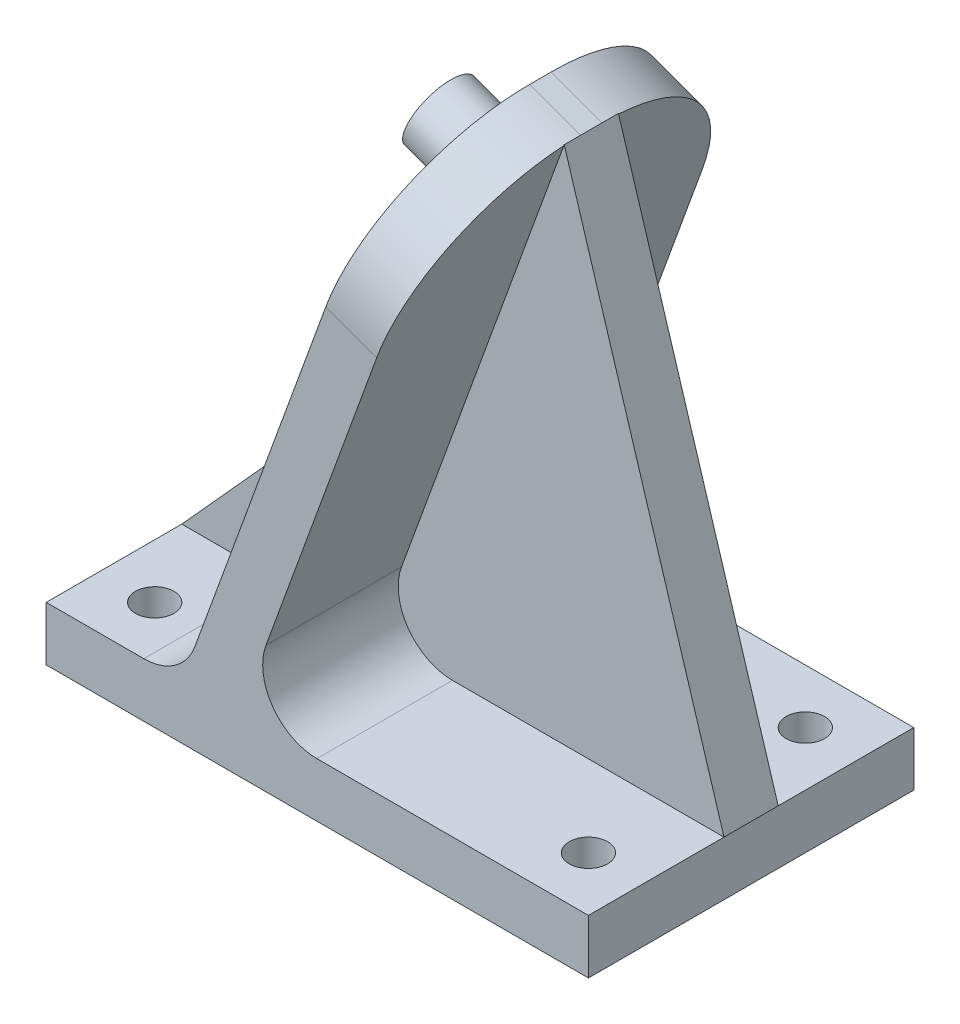
SolidWorks part; units mm, degrees
ref_plane "Front Plane" through (0, 0, 0) normal (0, 0, 1) x (1, 0, 0)
ref_plane "Top Plane" through (0, 0, 0) normal (0, 1, 0) x (1, 0, 0)
ref_plane "Right Plane" through (0, 0, 0) normal (1, 0, 0) x (0, 0, -1)
sketch "Sketch1" plane through (0, 0, 0) normal (0, 1, 0) x (1, 0, 0)
  line L1 (-31.75, -19.05) -> (31.75, -19.05)
  line L2 (-31.75, -19.05) -> (-31.75, 19.05)
  line L3 (-31.75, 19.05) -> (31.75, 19.05)
  line L4 (31.75, -19.05) -> (31.75, 19.05)
  line L5 (-31.75, -19.05) -> (31.75, 19.05) construction
  line L6 (-31.75, 19.05) -> (31.75, -19.05) construction
  point P0 (0, 0)
  dimension "D1" = 63.5
  dimension "D2" = 38.1
extrude "Boss-Extrude1" add sketch "Sketch1" along normal blind 6.35
sketch "Sketch2" plane through (0, 0, 19.05) normal (0, 0, 1) x (1, 0, 0)
  line L0 (-11.43, 0) -> (13.0366, 67.2214)
  line L1 (-11.43, 0) -> (-17.397, 2.1718)
  line L2 (13.0366, 67.2214) -> (7.0695, 69.3932)
  line L3 (-17.397, 2.1718) -> (7.0695, 69.3932)
  line L4 (-11.43, 0) -> (7.0695, 69.3932) construction
  line L5 (13.0366, 67.2214) -> (-17.397, 2.1718) construction
  line L6 (31.75, 6.35) -> (31.75, 0) construction
  line L7 (-31.75, 0) -> (31.75, 0) construction
  point P1 (-2.1802, 34.6966)
  dimension "D1" = 20
  dimension "D2" = 50.8
  dimension "D3" = 11.43
extrude "Boss-Extrude2" add sketch "Sketch2" against normal up to surface (38.1 mm away) up to face at (0, 3.175, -19.05)
fillet "Fillet1" radius 17.78 2 edges at (10.0531, 68.3073, 19.05) (10.0531, 68.3073, -19.05)
sketch "Sketch4" plane through (0, 6.35, 0) normal (0, 1, 0) x (1, 0, 0)
  circle A0 centre (25.4, -12.7) radius 2.25 construction
  circle A1 centre (-25.4, -12.7) radius 2.25 construction
  circle A2 centre (25.4, 12.7) radius 2.25 construction
  circle A3 centre (-25.4, 12.7) radius 2.25 construction
  circle A4 centre (25.4, -12.7) radius 2.25
  circle A5 centre (-25.4, -12.7) radius 2.25
  circle A6 centre (25.4, 12.7) radius 2.25
  circle A7 centre (-25.4, 12.7) radius 2.25
extrude "Cut-Extrude2" cut sketch "Sketch4" against normal through all
sketch "Sketch5" plane through (-16.06, 5.8454, 0) normal (-0.9397, 0.342, 0) x (0, 0, 1)
  line L0 (-1.27, 67.6262) -> (1.27, 67.6262) construction
  circle A0 centre (0, 54.9262) radius 5
  point P6 (0, 67.6262)
  dimension "D1" = 10
  dimension "D2" = 12.7
extrude "Boss-Extrude3" add sketch "Sketch5" along normal blind 1 contours A0 region at (2.7259, 57.4591, 0)
sketch "Sketch6" plane through (-16.9997, 6.1874, 0) normal (-0.9397, 0.342, 0) x (0, 0, 1)
  circle A0 centre (0, 54.9262) radius 4.05
  circle A1 centre (0, 54.9262) radius 5 construction
  dimension "D1" = 8.1
extrude "Boss-Extrude4" add sketch "Sketch6" along normal blind 7 contours A0 region at (1.7862, 57.8011, 0)
fillet "Fillet2" radius 6.35 2 edges at (-15.8763, 6.35, 0) (-9.1188, 6.35, 0)
sketch "Sketch7" plane through (0, 0, 0) normal (0, 0, 1) x (1, 0, 0)
  line L0 (13.0366, 67.2214) -> (31.75, 6.35)
  line L1 (-0.05, 6.35) -> (31.75, 6.35) construction
  line L2 (-6.0171, 14.8718) -> (6.9555, 50.5136) construction
  line L3 (6.9555, 50.5136) -> (13.0366, 67.2214) construction
  line L4 (-0.05, 6.35) -> (31.75, 6.35)
  line L5 (-6.0171, 14.8718) -> (6.9555, 50.5136)
  line L6 (6.9555, 50.5136) -> (13.0366, 67.2214)
  line L7 (-31.75, 6.35) -> (-5.1748, 35.7522)
  line L8 (0.9884, 52.6855) -> (-14.3556, 10.5282) construction
  line L9 (-31.75, 6.35) -> (-20.3226, 6.35) construction
  line L10 (-5.1748, 35.7522) -> (-14.3556, 10.5282)
  line L11 (-31.75, 6.35) -> (-20.3226, 6.35)
  line L12 (-6.1769, 56.3895) -> (0.401, 53.9954) construction
  arc A0 (-6.0171, 14.8718) -> (-0.05, 6.35) centre (-0.05, 12.7) ccw construction
  arc A1 (-6.0171, 14.8718) -> (-0.05, 6.35) centre (-0.05, 12.7) ccw
  arc A2 (-20.3226, 6.35) -> (-14.3556, 10.5282) centre (-20.3226, 12.7) ccw construction
  arc A3 (-20.3226, 6.35) -> (-14.3556, 10.5282) centre (-20.3226, 12.7) ccw
  dimension "D1" = 19.05
extrude "Boss-Extrude5" add sketch "Sketch7" along normal mid plane 6.35
